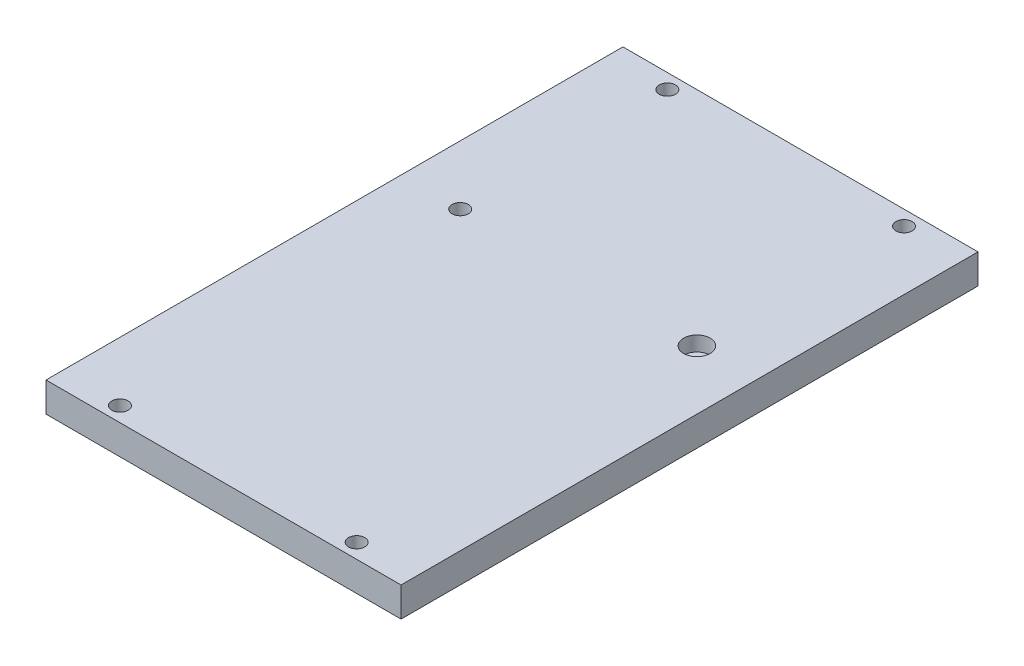
SolidWorks part; units mm, degrees
ref_plane "Front" through (0, 0, 0) normal (0, 0, 1) x (1, 0, 0)
ref_plane "Top" through (0, 0, 0) normal (0, 1, 0) x (1, 0, 0)
ref_plane "Right" through (0, 0, 0) normal (1, 0, 0) x (0, 0, -1)
sketch "Sketch1" plane through (0, 0, 0) normal (0, 1, 0) x (1, 0, 0)
  line L1 (-77.4278, 71.2487) -> (42.5722, 71.2487)
  line L2 (-77.4278, 71.2487) -> (-77.4278, -123.7513)
  line L3 (-77.4278, -123.7513) -> (42.5722, -123.7513)
  line L4 (42.5722, 71.2487) -> (42.5722, -123.7513)
  dimension "D1" = 120
  dimension "D2" = 195
extrude "Boss-Extrude1" add sketch "Sketch1" along normal blind 10
sketch "Sketch2" plane through (0, 10, 0) normal (0, 1, 0) x (-1, 0, 0)
  line L0 (77.4278, 123.7513) -> (-42.5722, 123.7513) construction
  line L1 (-42.5722, 123.7513) -> (-42.5722, -71.2487) construction
  line L2 (-42.5722, -71.2487) -> (77.4278, -71.2487) construction
  line L3 (77.4278, -71.2487) -> (77.4278, 123.7513) construction
  circle A0 centre (-22.5722, 118.7513) radius 2.75
  circle A1 centre (57.4278, 118.7513) radius 2.75
  circle A2 centre (-22.5722, 3.7513) radius 2.75
  circle A3 centre (57.4278, 3.7513) radius 2.75
  circle A4 centre (-22.5722, -66.2487) radius 2.75
  circle A5 centre (57.4278, -66.2487) radius 2.75
  dimension "D1" = 5.5
  dimension "D2" = 5
  dimension "D3" = 20
  dimension "D4" = 5
  dimension "D5" = 70
  dimension "D6" = 20
extrude "Cut-Extrude1" cut sketch "Sketch2" against normal through all
sketch "Sketch3" plane through (0, 10, 0) normal (0, 1, 0) x (-1, 0, 0)
  circle A0 centre (-22.5722, 3.7513) radius 4.5
  dimension "D1" = 9
extrude "Cut-Extrude2" cut sketch "Sketch3" against normal blind 5
